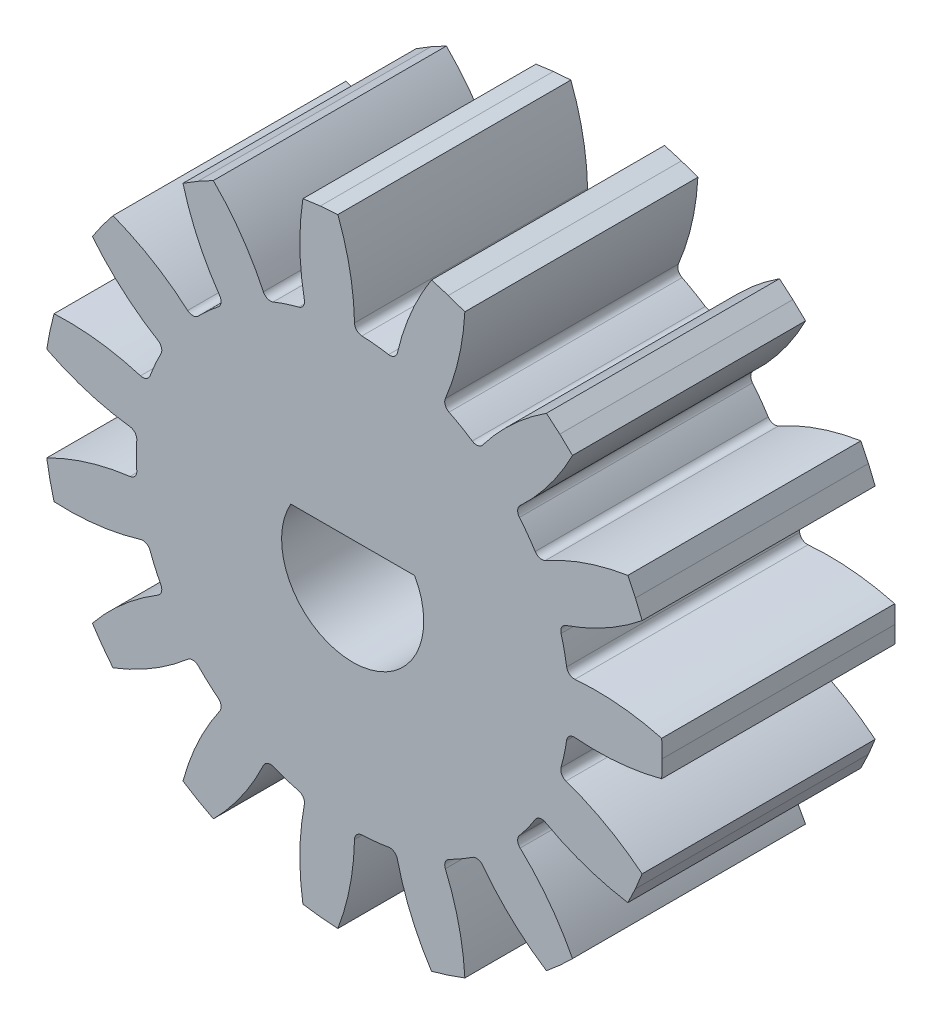
SolidWorks part; units mm, degrees
ref_plane "Front Plane" through (0, 0, 0) normal (0, 0, 1) x (1, 0, 0)
ref_plane "Top Plane" through (0, 0, 0) normal (0, 1, 0) x (1, 0, 0)
ref_plane "Right Plane" through (0, 0, 0) normal (1, 0, 0) x (0, 0, -1)
sketch "Sketch1" plane through (0, 0, 0) normal (0, 0, 1) x (1, 0, 0)
  line L0 (0, 0) -> (74.4139, 0) construction
  line L1 (0, 0) -> (9.0784, 1.9297) construction
  line L2 (0, 0) -> (74.4139, 8.4784) construction
  line L3 (0, 0) -> (74.4139, 4.2255) construction
  line L4 (13.2599, 0.753) -> (13.2812, 0)
  line L5 (0, 0) -> (9.0784, -1.9297) construction
  line L6 (0, 0) -> (9.0784, 1.9297)
  line L7 (0, 0) -> (9.0784, -1.9297) construction
  line L8 (0, 0) -> (9.0784, -1.9297)
  line L9 (13.2599, -0.753) -> (13.2812, 0)
  circle A0 centre (0, 0) radius 13.2812 construction
  circle A1 centre (0, 0) radius 11.7188 construction
  circle A2 centre (0, 0) radius 9.2812 construction
  arc A3 (9.2216, 1.0507) -> (13.2599, 0.753) centre (10.4542, -9.7675) cw
  arc A4 (9.2216, 1.0507) -> (9.0784, 1.9297) centre (0, 0) ccw
  arc A5 (9.2216, -1.0507) -> (9.0784, -1.9297) centre (0, 0) cw
  arc A6 (9.2216, -1.0507) -> (13.2599, -0.753) centre (10.4542, 9.7675) ccw
  dimension "D1" = 26.5625
  dimension "D2" = 1.5625
  dimension "D3" = 2.4375
  dimension "D4" = 12
  dimension "D5" = 6.5
  dimension "D6" = 3.25
extrude "Boss-Extrude1" add sketch "Sketch1" along normal blind 10
fillet "Fillet1" radius 0.3325 2 edges at (9.2216, 1.0507, 5) (9.2216, -1.0507, 5)
pattern_circular "CirPattern1" count 15 over 360 about axis through (0, 0, 10) along (0, 0, -1) of "Boss-Extrude1", "Fillet1"
sketch "Sketch2" plane through (0, 0, 0) normal (0, 0, -1) x (-1, 0, 0)
  line L0 (-2.6557, 1.5) -> (2.6557, 1.5)
  arc A0 (-2.6557, 1.5) -> (2.6557, 1.5) centre (0, 0) ccw
  point P1 (0, -3.05)
  dimension "D1" = 6.1
  dimension "D2" = 4.55
extrude "Cut-Extrude1" cut sketch "Sketch2" against normal up to next
